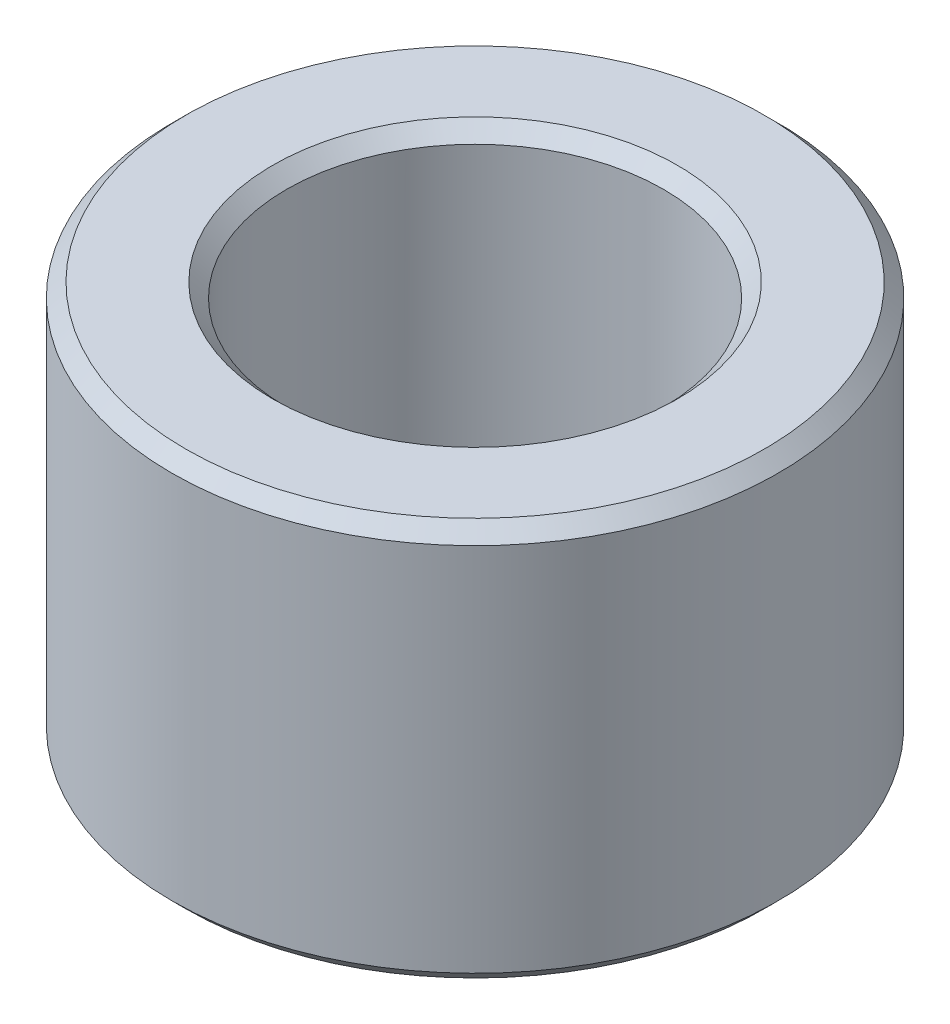
SolidWorks part; units mm, degrees
ref_plane "Front Plane" through (0, 0, 0) normal (0, 0, 1) x (1, 0, 0)
ref_plane "Top Plane" through (0, 0, 0) normal (0, 1, 0) x (1, 0, 0)
ref_plane "Right Plane" through (0, 0, 0) normal (1, 0, 0) x (0, 0, -1)
sketch "Sketch1" plane through (0, 0, 0) normal (0, 1, 0) x (1, 0, 0)
  circle A0 centre (0, 0) radius 40
  dimension "SLEEVE_OD" = 80
extrude "Boss-Extrude1" add sketch "Sketch1" along normal blind 52.5243
sketch "Sketch2" plane through (0, 0, 0) normal (0, 1, 0) x (1, 0, 0)
  circle A0 centre (0, 0) radius 24.8725
  dimension "BORE_D" = 49.745
extrude "Cut-Extrude1" cut sketch "Sketch2" along normal through all
chamfer "Chamfer1" distance 1.8339 angle 45 4 edges at (0, 52.5243, 24.8725) (0, 0, 24.8725) (0, 0, 40) (0, 52.5243, 40)
